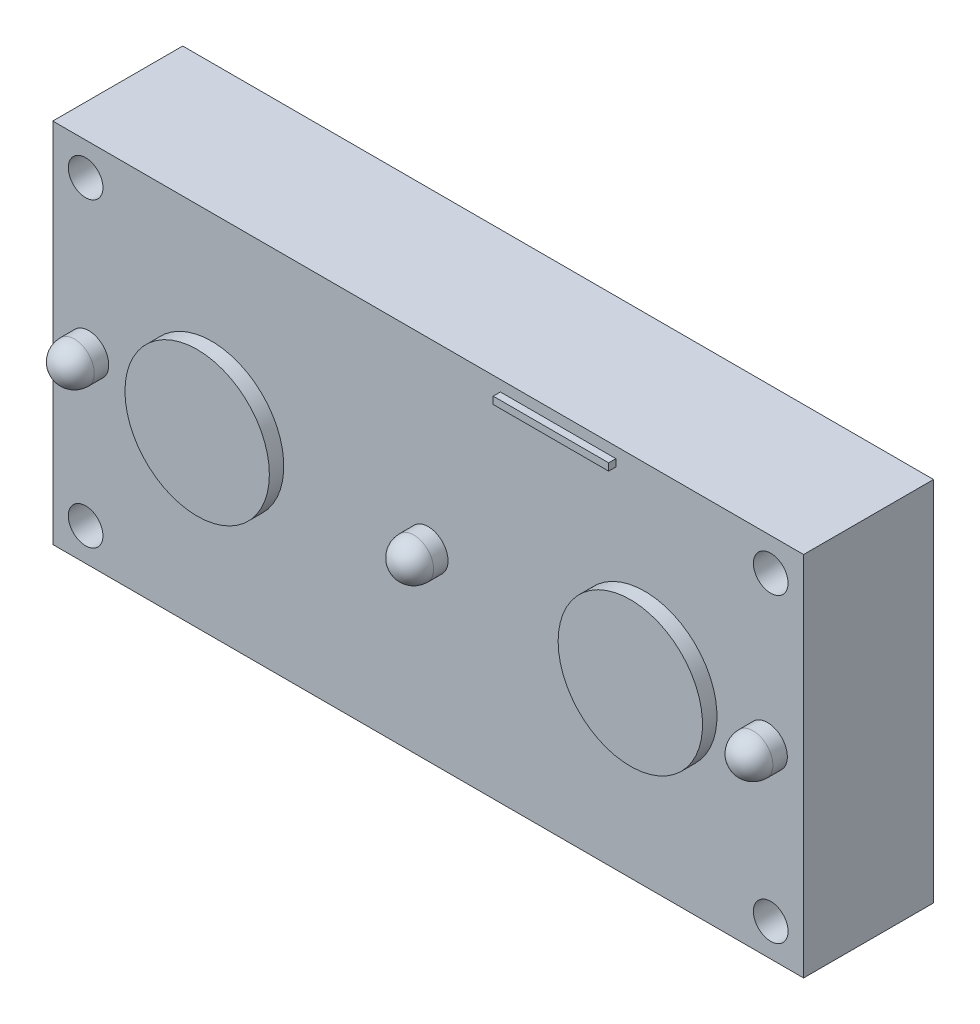
SolidWorks part; units mm, degrees
ref_plane "Piano frontale" through (0, 0, 0) normal (0, 0, 1) x (1, 0, 0)
ref_plane "Piano superiore" through (0, 0, 0) normal (0, 1, 0) x (1, 0, 0)
ref_plane "Piano destro" through (0, 0, 0) normal (1, 0, 0) x (0, 0, -1)
sketch "Schizzo1" plane through (0, 0, 0) normal (0, 0, 1) x (1, 0, 0)
  line L1 (-26, -12.7) -> (26, -12.7)
  line L2 (-26, -12.7) -> (-26, 12.7)
  line L3 (-26, 12.7) -> (26, 12.7)
  line L4 (26, -12.7) -> (26, 12.7)
  line L5 (-26, -12.7) -> (26, 12.7) construction
  line L6 (-26, 12.7) -> (26, -12.7) construction
  point P0 (0, 0)
  dimension "D1" = 52
  dimension "D2" = 25.4
extrude "Estrusione-Estrusione1" add sketch "Schizzo1" along normal blind 9
hole_wizard "Foro per Vite M2-1" positions "Schizzo3" profile "Schizzo4" hole size "M2" standard "Ansi Metric" end condition through all
sketch "Schizzo3" plane through (0, 0, 9) normal (0, 0, 1) x (1, 0, 0)
  line L1 (23.725, -10.44) -> (-23.725, -10.44) construction
  line L2 (23.725, -10.44) -> (23.725, 10.44) construction
  line L3 (23.725, 10.44) -> (-23.725, 10.44) construction
  line L4 (-23.725, -10.44) -> (-23.725, 10.44) construction
  line L6 (23.725, 10.44) -> (-23.725, -10.44) construction
  point P0 (-23.725, 10.44)
  point P3 (-23.725, -10.44)
  point P5 (23.725, -10.44)
  point P7 (23.725, 10.44)
  point P107 (0, 0)
  dimension "D1" = 47.45
  dimension "D2" = 20.88
sketch "Schizzo4" plane through (-23.725, 10.44, 9) normal (1, 0, 0) x (0, -1, 0)
  line L0 (0, 0) -> (0, 9)
  line L1 (0, 9) -> (1.2, 9)
  line L2 (1.2, 9) -> (1.2, 0)
  line L5 (1.2, 0) -> (0, 0)
  line L11 (0, -6.35) -> (0, 107.95) construction
  dimension "Thru Hole Dia." = 2.4
  dimension "Thru Hole Depth" = 9
sketch "Schizzo5" plane through (0, 0, 9) normal (0, 0, 1) x (1, 0, 0)
  line L0 (0, -12.7) -> (0, 12.7) construction
  line L1 (-26, -12.7) -> (26, -12.7) construction
  line L2 (26, 12.7) -> (-26, 12.7) construction
  circle A0 centre (-15, 0) radius 5
  circle A1 centre (15, 0) radius 5
  dimension "D1" = 10
  dimension "D2" = 30
extrude "Estrusione-Estrusione2" add sketch "Schizzo5" along normal blind 1
sketch "Schizzo6" plane through (0, 0, 9) normal (0, 0, 1) x (1, 0, 0)
  line L0 (26, -12.7) -> (26, 12.7) construction
  line L1 (13, 11.95) -> (5, 11.95)
  line L2 (13, 11.95) -> (13, 11.45)
  line L3 (13, 11.45) -> (5, 11.45)
  line L4 (5, 11.95) -> (5, 11.45)
  line L5 (26, 12.7) -> (-26, 12.7) construction
  dimension "D1" = 13
  dimension "D2" = 8
  dimension "D3" = 0.5
  dimension "D4" = 0.75
extrude "Estrusione-Estrusione3" add sketch "Schizzo6" along normal blind 0.5
sketch "Schizzo7" plane through (0, 0, 9) normal (0, 0, 1) x (1, 0, 0)
  line L0 (-26, 0) -> (-23.5, 0) construction
  line L1 (-26, 12.7) -> (-26, -12.7) construction
  line L2 (0, -12.7) -> (0, 12.7) construction
  line L3 (-26, -12.7) -> (26, -12.7) construction
  line L4 (26, 12.7) -> (-26, 12.7) construction
  circle A0 centre (-23.5, 0) radius 1.375
  circle A1 centre (23.5, 0) radius 1.375
  circle A2 centre (0, 0) radius 1.375
  dimension "D1" = 2.75
  dimension "D2" = 2.5
extrude "Estrusione-Estrusione4" add sketch "Schizzo7" along normal blind 1
dome "Cupola1" faces to dome 1 distance 1.375 reverse direction no elliptical dome no face at (-22.125, 0, 10) parameters "D1"=1.375
dome "Cupola2" faces to dome 1 distance 1.375 reverse direction no elliptical dome no face at (1.375, 0, 10) parameters "D1"=1.375
dome "Cupola3" faces to dome 1 distance 1.375 reverse direction no elliptical dome no face at (22.125, 0, 10) parameters "D1"=1.375
ref_plane "Piano1" through (0, -5, 0) normal (0, -1, 0) x (-1, 0, 0)
ref_plane "Piano2" through (0, -9.24, 0) normal (0, -1, 0) x (-1, 0, 0)
